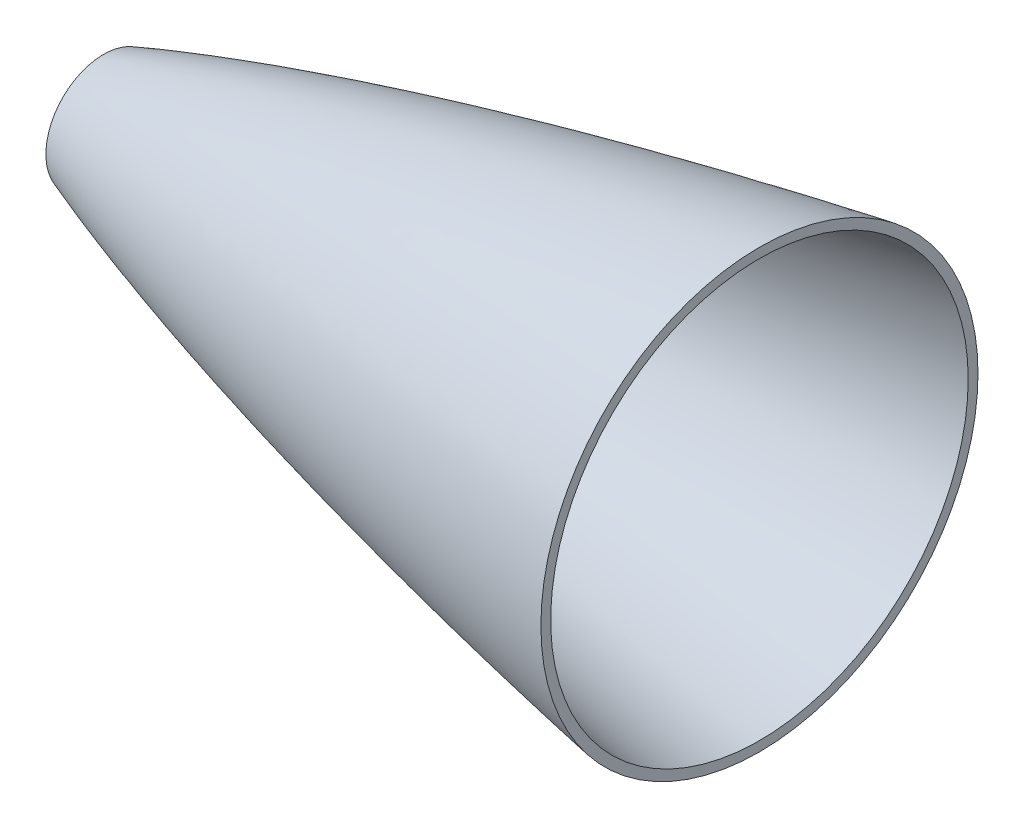
SolidWorks part; units mm, degrees
ref_plane "Front Plane" through (0, 0, 0) normal (0, 0, 1) x (1, 0, 0)
ref_plane "Top Plane" through (0, 0, 0) normal (0, 1, 0) x (1, 0, 0)
ref_plane "Right Plane" through (0, 0, 0) normal (1, 0, 0) x (0, 0, -1)
sketch "Sketch1" plane through (0, 0, 0) normal (0, 0, 1) x (1, 0, 0)
  line L0 (0, 0) -> (457.2, 0) construction
  line L2 (457.2, 95.25) -> (457.2, 0) construction
  line L3 (457.2, 0) -> (0, 0)
  line L5 (457.2, 0) -> (469.9, 0)
  line L7 (457.2, 95.25) -> (469.9, 95.25)
  line L8 (469.9, 0) -> (469.9, 95.25)
  spline S0 degree 4 poles (0, 0) (0.0023, 0.0126) (0.0082, 0.0373) (0.0262, 0.085) (0.0706, 0.1767) (0.1354, 0.2842) (0.2204, 0.4066) (0.336, 0.5565) (0.5083, 0.7608) (0.8021, 1.0733) (1.3251, 1.5652) (2.2381, 2.3192) (3.8253, 3.4666) (6.614, 5.2253) (11.4561, 7.8766) (19.2936, 11.6017) (32.6156, 17.1305) (51.6883, 23.9819) (75.6131, 31.5462) (103.3102, 39.362) (131.8924, 46.6864) (160.6143, 53.4403) (189.4482, 59.6969) (218.3767, 65.4994) (247.3876, 70.874) (276.4727, 75.8318) (305.6259, 80.3722) (334.843, 84.4812) (364.1216, 88.1294) (389.7928, 90.8706) (411.8341, 92.8374) (428.9951, 94.0676) (440.0323, 94.6976) (448.6181, 95.062) (453.5214, 95.2002) (455.9737, 95.2443) (457.2, 95.25) knots 0 0 0 0 0 0.000108 0.000216 0.000433 0.000866 0.001175 0.001483 0.002044 0.003139 0.004822 0.007588 0.012112 0.019791 0.032854 0.05453 0.085907 0.142462 0.205216 0.267971 0.330725 0.393479 0.456233 0.518987 0.581741 0.644496 0.70725 0.770004 0.832758 0.895512 0.926889 0.958267 0.979133 0.989567 1 1 1 1 1 construction
  spline S1 degree 4 poles (0, 0) (0.0023, 0.0126) (0.0082, 0.0373) (0.0262, 0.085) (0.0706, 0.1767) (0.1354, 0.2842) (0.2204, 0.4066) (0.336, 0.5565) (0.5083, 0.7608) (0.8021, 1.0733) (1.3251, 1.5652) (2.2381, 2.3192) (3.8253, 3.4666) (6.614, 5.2253) (11.4561, 7.8766) (19.2936, 11.6017) (32.6156, 17.1305) (51.6883, 23.9819) (75.6131, 31.5462) (103.3102, 39.362) (131.8924, 46.6864) (160.6143, 53.4403) (189.4482, 59.6969) (218.3767, 65.4994) (247.3876, 70.874) (276.4727, 75.8318) (305.6259, 80.3722) (334.843, 84.4812) (364.1216, 88.1294) (389.7928, 90.8706) (411.8341, 92.8374) (428.9951, 94.0676) (440.0323, 94.6976) (448.6181, 95.062) (453.5214, 95.2002) (455.9737, 95.2443) (457.2, 95.25) knots 0 0 0 0 0 0.000108 0.000216 0.000433 0.000866 0.001175 0.001483 0.002044 0.003139 0.004822 0.007588 0.012112 0.019791 0.032854 0.05453 0.085907 0.142462 0.205216 0.267971 0.330725 0.393479 0.456233 0.518987 0.581741 0.644496 0.70725 0.770004 0.832758 0.895512 0.926889 0.958267 0.979133 0.989567 1 1 1 1 1
  dimension "D1" = 457.2
  dimension "D2" = 95.25
  dimension "D3" = 12.7
revolve "Revolve1" add sketch "Sketch1" angle 360 about L3
shell "Shell1" thickness 3.175 removed face at (469.9, 0, -95.25)
ref_plane "Plane1" through (0, 0, 0) normal (1, 0, 0) x (0, 0, -1)
sketch "Sketch3" plane through (0, 0, 0) normal (1, 0, 0) x (0, 0, -1)
  circle A0 centre (0, 0) radius 95.25
extrude "Cut-Extrude1" cut sketch "Sketch3" along normal blind 38.1
sketch "Sketch4" plane through (469.9, 0, 0) normal (1, 0, 0) x (0, 0, -1)
  circle A0 centre (0, 0) radius 95.25 construction
  circle A1 centre (0, 0) radius 95.25
extrude "Cut-Extrude2" cut sketch "Sketch4" against normal blind 215.9
